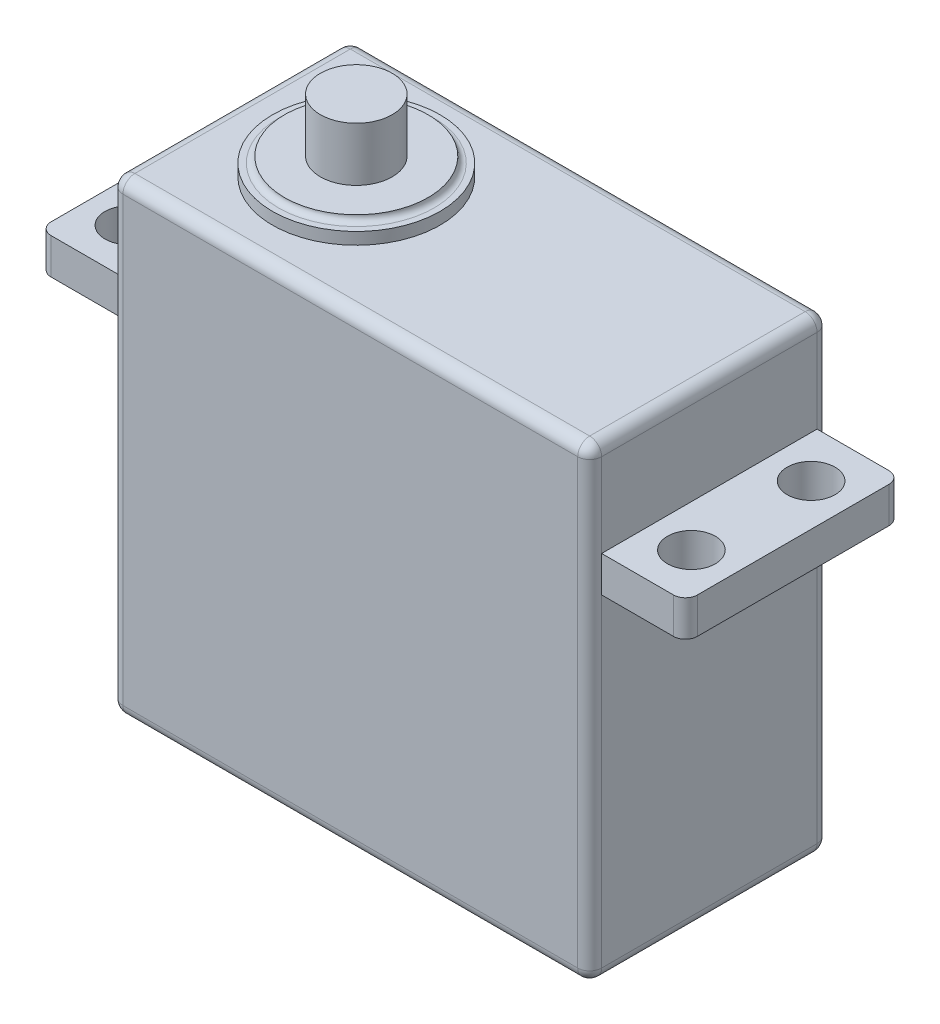
SolidWorks part; units mm, degrees
ref_plane "前视基准面" through (0, 0, 0) normal (0, 0, 1) x (1, 0, 0)
ref_plane "上视基准面" through (0, 0, 0) normal (0, 1, 0) x (1, 0, 0)
ref_plane "右视基准面" through (0, 0, 0) normal (1, 0, 0) x (0, 0, -1)
other "Configuration Table"
sketch "草图1" plane through (0, 0, 0) normal (0, 0, 1) x (1, 0, 0)
  line L1 (-18.7912, 29.9251) -> (21.2088, 29.9251)
  line L2 (-18.7912, 29.9251) -> (-18.7912, -9.0749)
  line L3 (-18.7912, -9.0749) -> (21.2088, -9.0749)
  line L4 (21.2088, 29.9251) -> (21.2088, -9.0749)
  dimension "D1" = 40
  dimension "D2" = 39
extrude "凸台-拉伸1" add sketch "草图1" along normal blind 20
fillet "圆角1" radius 1 12 edges at (21.2088, -9.0749, 10) (21.2088, 29.9251, 10) (1.2088, -9.0749, 0) (21.2088, 10.4251, 0) (1.2088, 29.9251, 0) (-18.7912, 29.9251, 10) (-18.7912, -9.0749, 10) (-18.7912, 10.4251, 0) (1.2088, 29.9251, 20) (21.2088, 10.4251, 20) (1.2088, -9.0749, 20) (-18.7912, 10.4251, 20)
sketch "草图2" plane through (-18.7912, 0, 0) normal (-1, 0, 0) x (0, 0, 1)
  line L1 (19, -8.0749) -> (19, 28.9251) construction
  line L2 (1, 28.9251) -> (1, -8.0749) construction
  line L3 (19, 21.9251) -> (1, 21.9251)
  line L4 (19, 21.9251) -> (19, 18.9251)
  line L5 (19, 18.9251) -> (1, 18.9251)
  line L6 (1, 21.9251) -> (1, 18.9251)
  dimension "D2" = 3
extrude "凸台-拉伸2" add sketch "草图2" along normal blind 7
sketch "草图3" plane through (21.2088, 0, 0) normal (1, 0, 0) x (0, 0, -1)
  line L1 (-1, -8.0749) -> (-1, 28.9251) construction
  line L2 (-19, 28.9251) -> (-19, -8.0749) construction
  line L3 (-1, 21.9251) -> (-19, 21.9251)
  line L4 (-1, 21.9251) -> (-1, 18.9251)
  line L5 (-1, 18.9251) -> (-19, 18.9251)
  line L6 (-19, 21.9251) -> (-19, 18.9251)
  dimension "D2" = 3
extrude "凸台-拉伸3" add sketch "草图3" along normal blind 7
fillet "圆角8" radius 1 1 edges at (28.2088, 20.4251, 1)
fillet "圆角9" radius 1 3 edges at (-25.7912, 20.4251, 1) (-25.7912, 20.4251, 19) (28.2088, 20.4251, 19)
sketch "草图4" plane through (0, 21.9251, 0) normal (0, 1, 0) x (1, 0, 0)
  circle A0 centre (-22.2912, -5) radius 2
extrude "切除-拉伸1" cut sketch "草图4" against normal blind 7
sketch "草图5" plane through (0, 21.9251, 0) normal (0, 1, 0) x (1, 0, 0)
  circle A0 centre (-22.2912, -15) radius 2
extrude "切除-拉伸2" cut sketch "草图5" against normal blind 7
sketch "草图6" plane through (0, 21.9251, 0) normal (0, 1, 0) x (1, 0, 0)
  circle A0 centre (24.7088, -5) radius 2
extrude "切除-拉伸3" cut sketch "草图6" against normal blind 7
sketch "草图8" plane through (0, 21.9251, 0) normal (0, 1, 0) x (1, 0, 0)
  circle A0 centre (24.7088, -15) radius 2
extrude "切除-拉伸4" cut sketch "草图8" against normal blind 7
sketch "草图9" plane through (0, 29.9251, 0) normal (0, 1, 0) x (1, 0, 0)
  circle A0 centre (-8.2912, -10) radius 3
extrude "凸台-拉伸4" add sketch "草图9" along normal blind 6
sketch "草图10" plane through (0, 29.9251, 0) normal (0, 1, 0) x (1, 0, 0)
  circle A0 centre (-8.2912, -10) radius 7
extrude "凸台-拉伸5" add sketch "草图10" along normal blind 1
sketch "草图11" plane through (0, 29.9251, 0) normal (0, 1, 0) x (1, 0, 0)
  circle A0 centre (-8.2912, -10) radius 6
extrude "凸台-拉伸6" add sketch "草图11" along normal blind 2
fillet "圆角11" radius 0.5 2 edges at (-8.2912, 31.9251, 16) (-8.2912, 30.9251, 16)
sketch "草图12" plane through (0, 0, 20) normal (0, 0, 1) x (1, 0, 0)
  line L0 (-2.2912, 31.4251) -> (-14.2912, 31.4251) construction
  line L1 (-14.2912, 31.4251) -> (-2.2912, 31.4251)
  line L2 (-14.2912, 31.4251) -> (-14.2912, 31.9251)
  line L3 (-14.2912, 31.9251) -> (-2.2912, 31.9251)
  line L4 (-2.2912, 31.4251) -> (-2.2912, 31.9251)
  arc A0 (-14.7912, 30.9251) -> (-14.2912, 31.4251) centre (-14.7912, 31.4251) ccw construction
  dimension "D1" = 12
  dimension "D2" = 0.5
extrude "切除-拉伸6" cut sketch "草图12" against normal blind 19
sketch "草图13" plane through (0, 35.9251, 0) normal (0, 1, 0) x (1, 0, 0)
  circle A0 centre (-8.2912, -10) radius 3
extrude "凸台-拉伸7" add sketch "草图13" against normal blind 6
